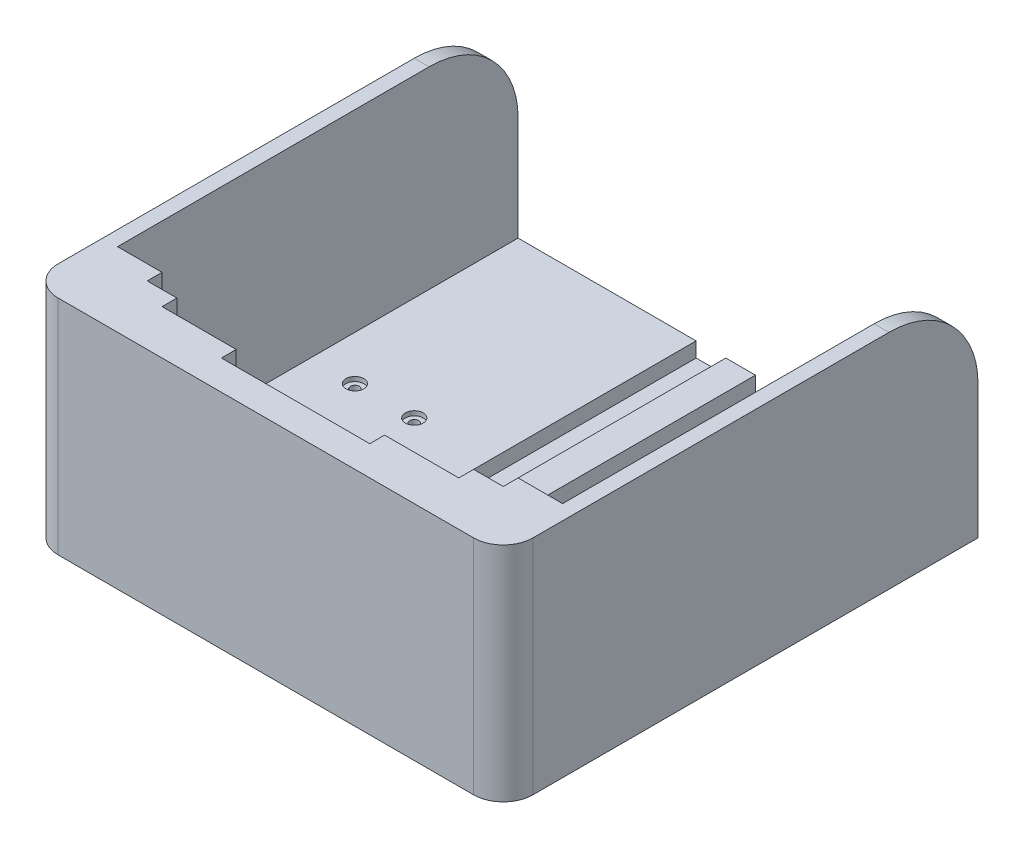
SolidWorks part; units mm, degrees
ref_plane "Front Plane" through (0, 0, 0) normal (0, 0, 1) x (1, 0, 0)
ref_plane "Top Plane" through (0, 0, 0) normal (0, 1, 0) x (1, 0, 0)
ref_plane "Right Plane" through (0, 0, 0) normal (1, 0, 0) x (0, 0, -1)
sketch "Sketch1" plane through (0, 0, 0) normal (0, 1, 0) x (1, 0, 0)
  line L1 (-80, 80) -> (80, 80)
  line L2 (-80, 80) -> (-80, -80)
  line L3 (-80, -80) -> (80, -80)
  line L4 (80, 80) -> (80, -80)
  line L5 (-80, 80) -> (80, -80) construction
  line L6 (-80, -80) -> (80, 80) construction
  point P0 (0, 0)
  dimension "D1" = 160
  dimension "D2" = 160
extrude "Boss-Extrude1" add sketch "Sketch1" along normal blind 75
sketch "Sketch2" plane through (0, 75, 0) normal (0, 1, 0) x (1, 0, 0)
  line L0 (-80, 80) -> (-80, -80) construction
  line L2 (-75, 80) -> (75, 80)
  line L4 (-75, 80) -> (-75, -70)
  line L5 (-75, -70) -> (75, -70)
  line L6 (75, 80) -> (75, -70)
  line L7 (80, -80) -> (80, 80) construction
  line L8 (80, 80) -> (-80, 80) construction
  line L9 (-80, -80) -> (80, -80) construction
  point P6 (0, 0)
  point P13 (0, 0)
  dimension "D1" = 5
  dimension "D2" = 5
  dimension "D3" = 0
  dimension "D4" = 10
extrude "Cut-Extrude1" cut sketch "Sketch2" against normal offset from surface (65 mm away) 10 up to face at (0, 0, 0)
sketch "Sketch3" plane through (0, 0, 70) normal (0, 0, -1) x (-1, 0, 0)
  line L0 (-75, 10) -> (75, 10) construction
  line L1 (-75, 75) -> (-60, 75)
  line L2 (-75, 75) -> (-75, 10)
  line L3 (-75, 10) -> (-60, 10)
  line L4 (-60, 75) -> (-60, 10)
  line L5 (0, 75) -> (0, 10) construction
  line L6 (75, 75) -> (-75, 75) construction
  line L7 (75, 10) -> (60, 10)
  line L8 (60, 75) -> (60, 10)
  line L9 (75, 75) -> (60, 75)
  line L10 (75, 75) -> (75, 10)
  dimension "D1" = 15
extrude "Boss-Extrude2" add sketch "Sketch3" along normal blind 15
sketch "Sketch4" plane through (0, 0, 70) normal (0, 0, -1) x (-1, 0, 0)
  line L0 (0, 75) -> (0, 10) construction
  line L1 (60, 75) -> (-60, 75) construction
  line L2 (75, 10) -> (-75, 10) construction
  line L3 (-60, 10) -> (60, 10) construction
  line L4 (-60, 75) -> (-50, 75)
  line L5 (-60, 75) -> (-60, 10)
  line L6 (-60, 10) -> (-50, 10)
  line L7 (-50, 75) -> (-50, 10)
  line L8 (60, 10) -> (50, 10)
  line L9 (50, 75) -> (50, 10)
  line L10 (60, 75) -> (50, 75)
  line L11 (60, 75) -> (60, 10)
  dimension "D1" = 10
extrude "Boss-Extrude3" add sketch "Sketch4" along normal blind 10
fillet "Fillet1" radius 10 2 edges at (80, 37.5, 80) (-80, 37.5, 80)
sketch "Sketch11" plane through (0, 0, 70) normal (0, 0, -1) x (-1, 0, 0)
  line L0 (-50, 10) -> (50, 10) construction
  line L1 (-50, 75) -> (-25, 75)
  line L2 (-50, 75) -> (-50, 10)
  line L3 (-50, 10) -> (-25, 10)
  line L4 (-25, 75) -> (-25, 10)
  line L5 (0, 75) -> (0, 10) construction
  line L6 (50, 75) -> (-50, 75) construction
  line L7 (75, 10) -> (-75, 10) construction
  line L8 (50, 10) -> (25, 10)
  line L9 (25, 75) -> (25, 10)
  line L10 (50, 75) -> (25, 75)
  line L11 (50, 75) -> (50, 10)
  dimension "D1" = 25
extrude "Boss-Extrude4" add sketch "Sketch11" along normal blind 5
fillet "Fillet2" radius 30 2 edges at (-77.5, 75, -80) (77.5, 75, -80)
sketch "Sketch15" plane through (0, 0, 0) normal (0, -1, 0) x (1, 0, 0)
  line L0 (-80, 0) -> (80, 0) construction
  line L1 (80, 70) -> (80, -80) construction
  line L2 (0, 0) -> (0, 80) construction
  line L3 (-70, 80) -> (70, 80) construction
  line L4 (-80, -80) -> (-80, 70) construction
  circle A0 centre (-60, 10) radius 1.5
  circle A1 centre (-40, 10) radius 1.5
  circle A2 centre (40, 10) radius 1.5
  circle A3 centre (60, 10) radius 1.5
  circle A4 centre (60, -10) radius 1.5
  circle A5 centre (40, -10) radius 1.5
  circle A6 centre (-40, -10) radius 1.5
  circle A7 centre (-60, -10) radius 1.5
  point P6 (0, 0)
  dimension "D1" = 3
  dimension "D2" = 3
  dimension "D3" = 20
  dimension "D4" = 10
  dimension "D5" = 20
extrude "Cut-Extrude2" cut sketch "Sketch15" against normal up to surface (10 mm away) up to face at (0, 10, 43.75)
sketch "Sketch17" plane through (0, 10, 0) normal (0, 1, 0) x (1, 0, 0)
  line L0 (-60, 10) -> (-40, 10) construction
  line L1 (-40, 10) -> (-40, -10) construction
  line L2 (-50, 10) -> (-50, -10) construction
  line L3 (-40, 0) -> (-59.8059, 0) construction
  line L4 (0, 24.5779) -> (0, -24.5779) construction
  circle A1 centre (-60, 10) radius 3
  circle A2 centre (-40, 10) radius 3
  circle A3 centre (-40, -10) radius 3
  circle A4 centre (-60, -10) radius 3
  circle A5 centre (40, -10) radius 3
  circle A6 centre (60, -10) radius 3
  circle A7 centre (40, 10) radius 3
  circle A8 centre (60, 10) radius 3
  point P19 (0, 0)
  dimension "D1" = 6
extrude "Cut-Extrude3" cut sketch "Sketch17" against normal blind 1.5
sketch "Sketch18" plane through (0, 10, 0) normal (0, 1, 0) x (1, 0, 0)
  line L0 (0, 80) -> (0, -70) construction
  line L1 (-75, 80) -> (75, 80) construction
  line L2 (25, -70) -> (-25, -70) construction
  line L3 (-25, -70) -> (25, -70) construction
  line L4 (5, 80) -> (15, 80)
  line L5 (5, 80) -> (5, -65)
  line L6 (5, -65) -> (15, -65)
  line L7 (15, 80) -> (15, -65)
  line L8 (-5, -65) -> (-15, -65)
  line L9 (-15, 80) -> (-15, -65)
  line L10 (-5, 80) -> (-15, 80)
  line L11 (-5, 80) -> (-5, -65)
  dimension "D1" = 10
  dimension "D2" = 0
  dimension "D3" = 10
  dimension "D4" = 5
extrude "Cut-Extrude6" cut sketch "Sketch18" against normal blind 5
sketch "Sketch19" plane through (0, 0, 0) normal (0, -1, 0) x (1, 0, 0)
  line L0 (-60, 10) -> (-40, 10) construction
  line L1 (-40, 10) -> (-40, -10) construction
  line L2 (-50, 10) -> (-50, -10) construction
  line L3 (-40, 0) -> (-59.8059, 0) construction
  line L4 (40, 10) -> (60, 10) construction
  line L5 (60, 10) -> (60, -10) construction
  line L6 (50, 10) -> (50, -10) construction
  line L7 (60, 0) -> (39.8059, 0) construction
  point P21 (-50, 0)
  point P22 (50, 0)
  dimension "D1" = 100
